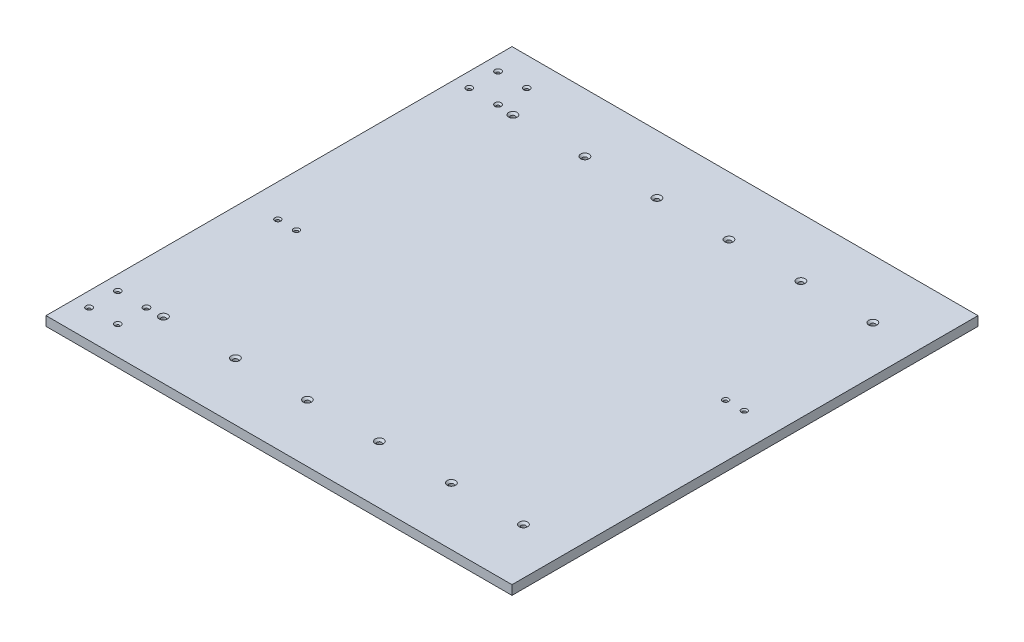
SolidWorks part; units mm, degrees
material "Buk"
ref_plane "Płaszczyzna przednia" through (0, 0, 0) normal (0, 0, 1) x (1, 0, 0)
ref_plane "Płaszczyzna górna" through (0, 0, 0) normal (0, 1, 0) x (1, 0, 0)
ref_plane "Płaszczyzna prawa" through (0, 0, 0) normal (1, 0, 0) x (0, 0, -1)
sketch "Szkic1" plane through (0, 0, 0) normal (0, 1, 0) x (1, 0, 0)
  line L1 (0, 0) -> (500, 0)
  line L2 (0, 0) -> (0, 500)
  line L3 (0, 500) -> (500, 500)
  line L4 (500, 0) -> (500, 500)
  dimension "D1" = 500
extrude "Dodanie-wyciągnięcie1" add sketch "Szkic1" along normal blind 10
sketch "Szkic2" plane through (0, 10, 0) normal (0, 1, 0) x (1, 0, 0)
  line L0 (0, 0) -> (500, 0) construction
  line L1 (0, 500) -> (0, 0) construction
  line L2 (0, 250) -> (500, 250) construction
  line L3 (500, 0) -> (500, 500) construction
  circle A0 centre (15.6, 30.6) radius 1.6
  circle A1 centre (15.6, 61.4) radius 1.6
  circle A2 centre (46.4, 61.4) radius 1.6
  circle A3 centre (46.4, 30.6) radius 1.6
  circle A4 centre (15.6, 438.6) radius 1.6
  circle A5 centre (15.6, 469.4) radius 1.6
  circle A6 centre (46.4, 469.4) radius 1.6
  circle A7 centre (46.4, 438.6) radius 1.6
  dimension "D1" = 3.2
  dimension "D2" = 3.2
  dimension "D3" = 3.2
  dimension "D4" = 3.2
  dimension "D5" = 30.6
  dimension "D6" = 30.6
  dimension "D7" = 30.8
  dimension "D8" = 15.6
  dimension "D9" = 15.6
  dimension "D10" = 30.8
  dimension "D11" = 30.8
  dimension "D12" = 30.8
hole_wizard "Pogłębienie stożkowe pod M3 Wkręt ustalający1" positions "Szkic3" profile "Szkic5" countersink size "M3" standard "Ansi Metric"
sketch "Szkic3" plane through (0, 10, 0) normal (0, 1, 0) x (1, 0, 0)
  point P0 (46.4, 30.6)
  point P3 (46.4, 61.4)
  point P6 (15.6, 61.4)
  point P9 (15.6, 30.6)
  point P12 (46.4, 438.6)
  point P15 (46.4, 469.4)
  point P18 (15.6, 469.4)
  point P21 (15.6, 438.6)
sketch "Szkic5" plane through (46.4, 10, -30.6) normal (1, 0, 0) x (0, 0, 1)
  line L0 (0, 0) -> (0, 11.0215)
  line L1 (0, 11.0215) -> (1.7, 10)
  line L2 (1.7, 10) -> (1.7, 1.66)
  line L3 (1.7, 1.66) -> (3.36, 0)
  line L5 (3.36, 0) -> (0, 0)
  line L6 (-1.7, 1.66) -> (-3.36, 0) construction
  line L10 (0, 11.0215) -> (-1.7, 10) construction
  line L11 (0, -6.35) -> (0, 107.95) construction
  dimension "Œrednica otworu" = 3.4
  dimension "G³êbokoœc otworu" = 10
  dimension "Œrednica zewnêtrznego pog³êbienia sto¿kowego" = 6.72
  dimension "K¹t zewnêtrznego pog³êbienia sto¿kowego" = 90
  dimension "K¹t wiert³a" = 118
hole_wizard "Pogłębienie stożkowe pod M4 Wkręt ustalający1" positions "Szkic6" profile "Szkic7" countersink size "M4" standard "Ansi Metric"
sketch "Szkic6" plane through (0, 10, 0) normal (0, 1, 0) x (1, 0, 0)
  line L0 (0, 500) -> (0, 0) construction
  line L1 (0, 0) -> (500, 0) construction
  point P0 (63.9, 62.07)
  point P14 (141.15, 62.07)
  point P15 (218.4, 62.07)
  point P16 (295.65, 62.07)
  point P17 (372.9, 62.07)
  point P18 (450.15, 62.07)
  point P19 (141.15, 437.07)
  point P20 (218.4, 437.07)
  point P21 (295.65, 437.07)
  point P22 (372.9, 437.07)
  point P23 (450.15, 437.07)
  point P24 (63.9, 437.07)
  dimension "D1" = 63.9
  dimension "D2" = 62.07
  dimension "D3" = 6
  dimension "D4" = 2
sketch "Szkic7" plane through (63.9, 10, -62.07) normal (1, 0, 0) x (0, 0, 1)
  line L0 (0, 0) -> (0, 12.9421)
  line L1 (0, 12.9421) -> (2.4, 11.5)
  line L2 (2.4, 11.5) -> (2.4, 2.08)
  line L3 (2.4, 2.08) -> (4.48, 0)
  line L5 (4.48, 0) -> (0, 0)
  line L6 (-2.4, 2.08) -> (-4.48, 0) construction
  line L10 (0, 12.9421) -> (-2.4, 11.5) construction
  line L11 (0, -6.35) -> (0, 107.95) construction
  dimension "Œrednica otworu" = 4.8
  dimension "G³êbokoœc otworu" = 11.5
  dimension "Œrednica zewnêtrznego pog³êbienia sto¿kowego" = 8.96
  dimension "K¹t zewnêtrznego pog³êbienia sto¿kowego" = 90
  dimension "K¹t wiert³a" = 118
sketch "Szkic8" plane through (0, 0, 0) normal (0, -1, 0) x (1, 0, 0)
  line L0 (0, -500) -> (0, 0) construction
  line L1 (60, -37) -> (460, -37)
  line L2 (60, -37) -> (60, -47)
  line L3 (60, -47) -> (460, -47)
  line L4 (460, -37) -> (460, -47)
  line L5 (0, 0) -> (500, 0) construction
  line L6 (60, -77) -> (60, -87)
  line L7 (60, -77) -> (460, -77)
  line L8 (460, -77) -> (460, -87)
  line L9 (60, -87) -> (460, -87)
  line L10 (60, -452) -> (60, -462)
  line L11 (60, -462) -> (460, -462)
  line L12 (460, -452) -> (460, -462)
  line L13 (60, -452) -> (460, -452)
  line L14 (60, -412) -> (60, -422)
  line L15 (60, -412) -> (460, -412)
  line L16 (460, -412) -> (460, -422)
  line L17 (60, -422) -> (460, -422)
  dimension "D1" = 10
  dimension "D2" = 400
  dimension "D3" = 60
  dimension "D4" = 2
  dimension "37" = 37
  dimension "D5" = 10
  dimension "D6" = 375
extrude "Wytnij-wyciągnięcie1" cut sketch "Szkic8" against normal blind 1
fillet "Zaokrąglenie1" radius 2 16 edges at (460, 1, -457) (260, 1, -462) (60, 1, -457) (260, 1, -452) (460, 1, -417) (260, 1, -422) (60, 1, -417) (260, 1, -412) (460, 1, -82) (260, 1, -87) (60, 1, -82) (260, 1, -77) (260, 1, -37) (460, 1, -42) (260, 1, -47) (60, 1, -42)
sketch "Sketch1" plane through (0, 0, 0) normal (0, -1, 0) x (1, 0, 0)
  line L0 (0, 0) -> (500, 0) construction
  line L1 (500, 0) -> (500, -500) construction
  line L2 (500, -500) -> (0, -500) construction
  circle A0 centre (468, -46) radius 5
  circle A1 centre (468, -454) radius 5
  dimension "D1" = 46
  dimension "D2" = 10
  dimension "D3" = 32
  dimension "D5" = 10
  dimension "D6" = 32
  dimension "D4" = 46
extrude "Cut-Extrude1" cut sketch "Sketch1" against normal blind 4
hole_wizard "CSK for M3 Flat Head Machine Screw1" positions "Sketch2" profile "Sketch3" countersink size "M3" standard "ANSI Metric" end condition through all
sketch "Sketch2" plane through (0, 10, 0) normal (0, -1, 0) x (-1, 0, 0)
  point P0 (-35, 213.747)
  point P3 (-55, 213.747)
  point P6 (-442.9854, 286.253)
  point P9 (-462.9854, 286.253)
  point P13 (0, 0)
sketch "Sketch3" plane through (35, 10, -213.747) normal (1, 0, 0) x (0, 0, 1)
  line L0 (0, 0) -> (0, 10)
  line L1 (0, 10) -> (1.8, 10)
  line L2 (1.8, 10) -> (1.8, 1.35)
  line L3 (1.8, 1.35) -> (3.15, 0)
  line L5 (3.15, 0) -> (0, 0)
  line L6 (-1.8, 1.35) -> (-3.15, 0) construction
  line L11 (0, -6.35) -> (0, 107.95) construction
  dimension "Thru Hole Dia." = 3.6
  dimension "Thru Hole Depth" = 10
  dimension "Near C'Sink Dia." = 6.3
  dimension "Near C'Sink Angle" = 90
